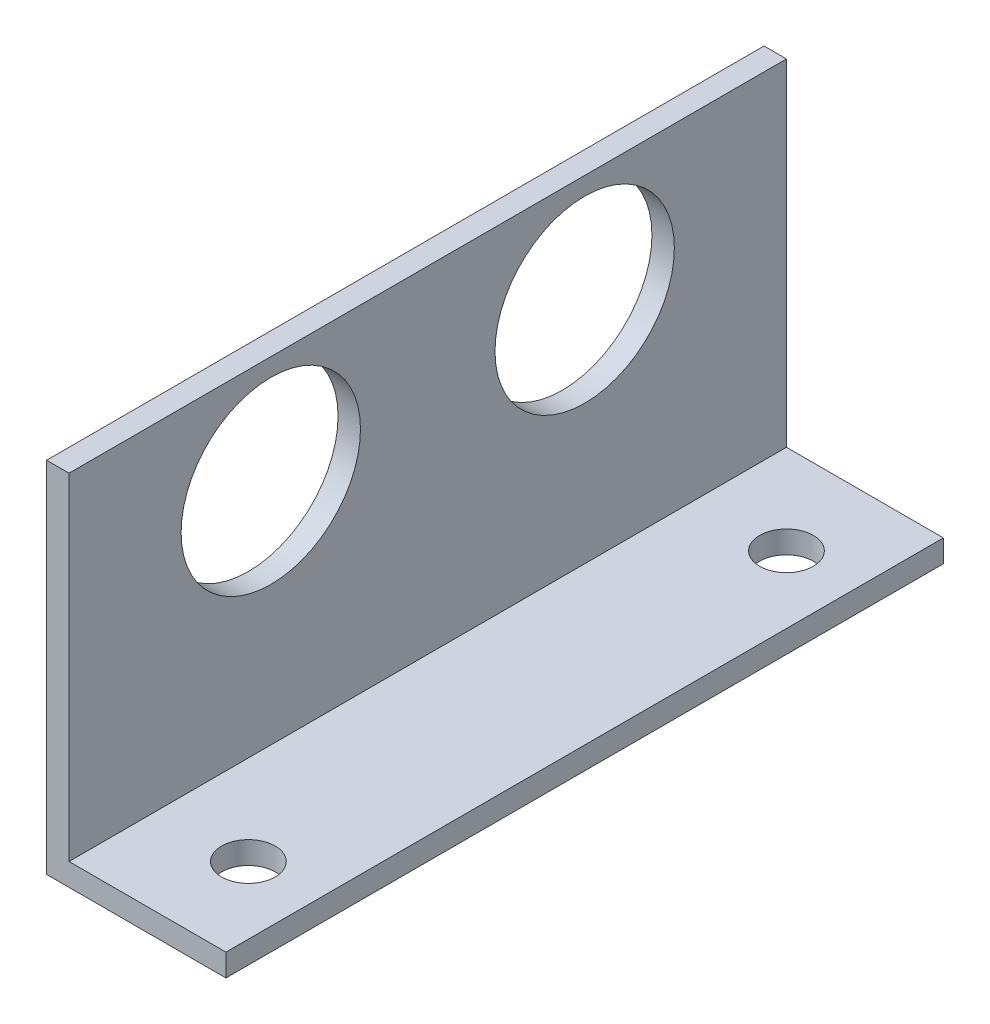
SolidWorks part; units mm, degrees
ref_plane "Front Plane" through (0, 0, 0) normal (0, 0, 1) x (1, 0, 0)
ref_plane "Top Plane" through (0, 0, 0) normal (0, 1, 0) x (1, 0, 0)
ref_plane "Right Plane" through (0, 0, 0) normal (1, 0, 0) x (0, 0, -1)
sketch "Sketch1" plane through (0, 0, 0) normal (0, 0, 1) x (1, 0, 0)
  line L0 (0, 0) -> (12.7, 0)
  line L1 (55, 0) -> (-55, 0) construction
  line L2 (12.7, 0) -> (12.7, 1.5875)
  line L3 (12.7, 1.5875) -> (1.5875, 1.5875)
  line L4 (1.5875, 1.5875) -> (1.5875, 25.4)
  line L5 (1.5875, 25.4) -> (0, 25.4)
  line L6 (0, -55) -> (0, 55) construction
  line L7 (0, 25.4) -> (0, 0)
  dimension "D1" = 1.5875
  dimension "D2" = 12.7
  dimension "D3" = 25.4
extrude "Boss-Extrude1" add sketch "Sketch1" along normal mid plane 50.8
sketch "Sketch3" plane through (0, 0, 0) normal (-1, 0, 0) x (0, 0, 1)
  line L0 (0, 0) -> (0, 17.78) construction
  line L1 (0, 17.78) -> (11.1125, 17.78) construction
  line L2 (0, 17.78) -> (-11.1125, 17.78) construction
  line L3 (25.4, 0) -> (-25.4, 0) construction
  circle A0 centre (11.1125, 17.78) radius 6.35
  circle A1 centre (-11.1125, 17.78) radius 6.35
  dimension "D1" = 12.7
  dimension "D2" = 22.225
  dimension "D3" = 17.78
extrude "Cut-Extrude1" cut sketch "Sketch3" against normal through all
sketch "Sketch5" plane through (0, 1.5875, 0) normal (0, 1, 0) x (1, 0, 0)
  line L0 (1.5875, 0) -> (7.9375, 0) construction
  line L1 (1.5875, -25.4) -> (1.5875, 25.4) construction
  line L2 (7.9375, 0) -> (7.9375, 19.05) construction
  line L3 (7.9375, 0) -> (7.9375, -19.05) construction
  line L4 (12.7, 25.4) -> (1.5875, 25.4) construction
  dimension "D1" = 6.35
  dimension "D2" = 6.35
hole_wizard "#6 Clearance Hole1" positions "Sketch10" profile "Sketch9" hole size "#6" standard "ANSI Inch"
sketch "Sketch10" plane through (0, 1.5875, 0) normal (0, 1, 0) x (1, 0, 0)
  point P0 (7.9375, 19.05)
  point P3 (7.9375, -19.05)
sketch "Sketch9" plane through (7.9375, 1.5875, -19.05) normal (1, 0, 0) x (0, 0, 1)
  line L0 (0, 0) -> (0, 4.3158)
  line L1 (0, 4.3158) -> (1.8986, 3.175)
  line L2 (1.8986, 3.175) -> (1.8986, 0)
  line L5 (1.8986, 0) -> (0, 0)
  line L10 (0, 4.3158) -> (-1.8986, 3.175) construction
  line L11 (0, -6.35) -> (0, 107.95) construction
  dimension "Hole Dia." = 3.7973
  dimension "Hole Depth" = 3.175
  dimension "Drill Angle" = 118
